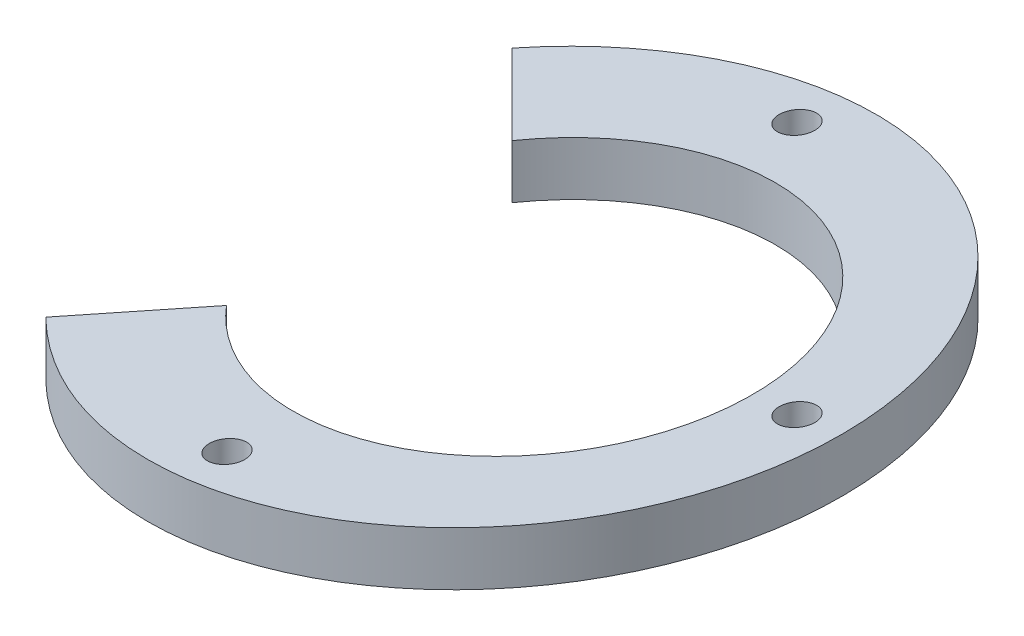
SolidWorks part; units mm, degrees
ref_plane "Front Plane" through (0, 0, 0) normal (0, 0, 1) x (1, 0, 0)
ref_plane "Top Plane" through (0, 0, 0) normal (0, 1, 0) x (1, 0, 0)
ref_plane "Right Plane" through (0, 0, 0) normal (1, 0, 0) x (0, 0, -1)
sketch "Sketch1" plane through (0, 0, 0) normal (0, 1, 0) x (1, 0, 0)
  line L0 (-37, 0) -> (-27, 0) construction
  line L1 (-11.863, 11.863) -> (11.863, -11.863)
  line L2 (0, 0) -> (13.2345, 0) construction
  line L3 (0, -27) -> (0, -37) construction
  line L4 (-27, 0) -> (-22, 0) construction
  line L5 (-22, 0) -> (27, 0) construction
  circle A0 centre (0, 0) radius 37
  circle A1 centre (0, 0) radius 27
  circle A3 centre (-32, 0) radius 2
  circle A4 centre (0, -32) radius 2
  circle A5 centre (32, 0) radius 2
  circle A6 centre (0, 32) radius 2
  circle A7 centre (2.5, 0) radius 24.5
  point P11 (0, 0)
  dimension "D1" = 74
  dimension "D2" = 54
  dimension "D3" = 4
  dimension "D5" = 4
  dimension "D6" = 5
  dimension "D4" = 45
extrude "Boss-Extrude1" add sketch "Sketch1" along normal blind 50 contours A0 A5 A4 A3 A1 A6 | A1 A7 region at (-35.9535, 0, 0) region at (-26.2363, 0, 0)
sketch "Sketch2" plane through (0, 0, 0) normal (0, 0, 1) x (1, 0, 0)
  line L0 (-37, 0) -> (37, 8.3004)
  line L1 (37, 0) -> (37, 50) construction
  line L2 (-37, 6.0376) -> (37, 14.3381)
  line L3 (-37, 50) -> (-37, 0) construction
  line L4 (-37, 0) -> (37, 0)
  line L5 (-37, 6.0376) -> (-37, 0)
  line L6 (37, 14.3381) -> (37, 8.3004)
  line L7 (-37, 6.0376) -> (-37, 50)
  line L8 (-37, 50) -> (37, 50)
  line L9 (37, 50) -> (37, 14.3381)
  line L10 (37, 0) -> (37, 8.3004)
  dimension "D1" = 6.4
  dimension "D2" = 6
extrude "Cut-Extrude1" cut sketch "Sketch2" against normal mid plane 1000 contours L9 L8 L7 L2 | L4 L10 L0 region at (12.3333, 2.7668, 0) region at (-1.2857, 30.0218, 0)
ref_plane "Plane1" through (-0.6827, 6.0862, 0) normal (-0.1115, 0.9938, 0) x (0.9938, 0.1115, 0)
sketch "Sketch4" plane through (0, 0, 0) normal (0, 1, 0) x (1, 0, 0)
  circle A0 centre (-32, 0) radius 3.5
  circle A1 centre (0, 32) radius 3.5
  circle A2 centre (32, 0) radius 3.5
  circle A3 centre (0, -32) radius 3.5
  dimension "D1" = 7
  dimension "D2" = 7
  dimension "D3" = 7
  dimension "D4" = 7
extrude "Cut-Extrude2" cut sketch "Sketch4" along normal up to surface (2.5734 mm away) up to plane "Plane1"
sketch "Sketch6" plane through (0, 0, 0) normal (0, 1, 0) x (1, 0, 0)
  line L0 (0, 0) -> (-37, 0) construction
  line L1 (0, 0) -> (-26.163, 26.163)
  line L2 (0, 0) -> (-26.163, -26.163)
  circle A0 centre (0, 0) radius 37 construction
  circle A1 centre (0, 0) radius 37
extrude "Cut-Extrude3" cut sketch "Sketch6" along normal blind 10 contours L2 L0 A1 | L0 L1 A1 region at (-22.2078, 0, 9.1988) region at (-22.2078, 0, -9.1988)
